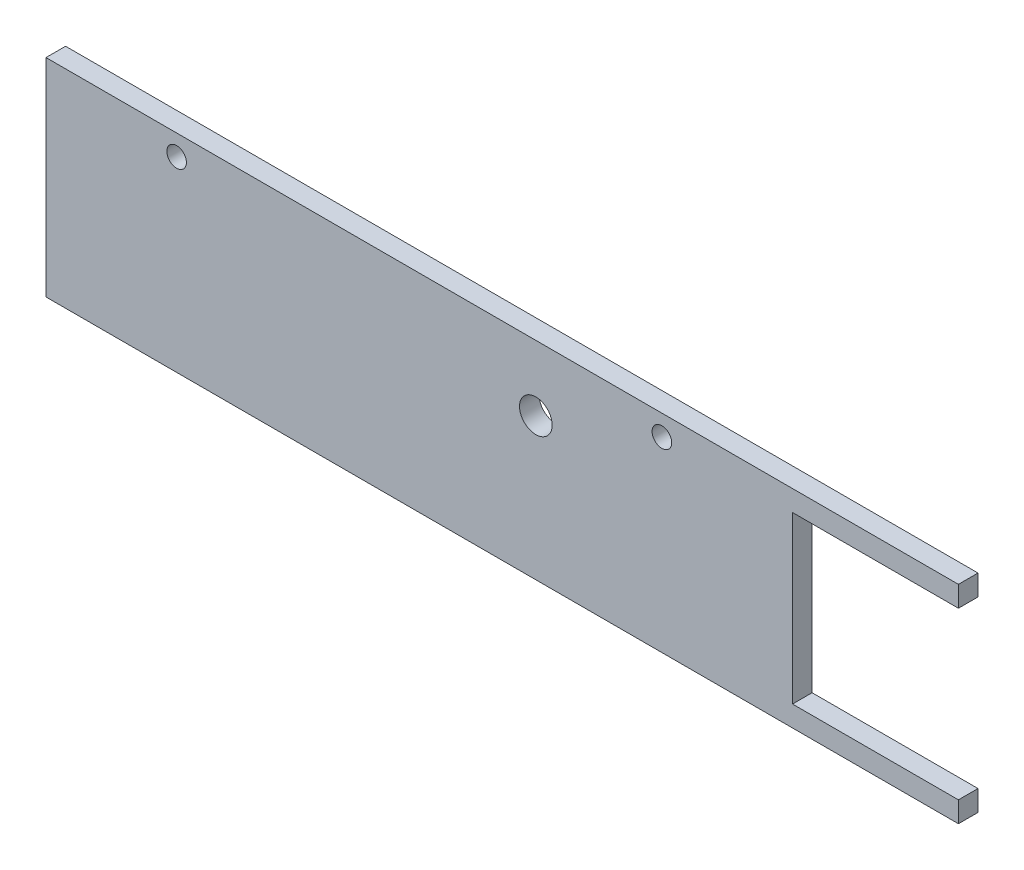
SolidWorks part; units mm, degrees
material "PET"
ref_plane "Front Plane" through (0, 0, 0) normal (0, 0, 1) x (1, 0, 0)
ref_plane "Top Plane" through (0, 0, 0) normal (0, 1, 0) x (1, 0, 0)
ref_plane "Right Plane" through (0, 0, 0) normal (1, 0, 0) x (0, 0, -1)
sketch "Sketch2" plane through (0, 0, 0) normal (0, 0, 1) x (1, 0, 0)
  line L1 (0, 0) -> (-139.7, 0)
  line L2 (0, 0) -> (0, -31.75)
  line L3 (0, -31.75) -> (-139.7, -31.75)
  line L4 (-139.7, 0) -> (-139.7, -31.75)
  dimension "D1" = 31.75
  dimension "D2" = 139.7
extrude "Boss-Extrude1" add sketch "Sketch2" along normal blind 3
sketch "Sketch3" plane through (0, 0, 3) normal (0, 0, 1) x (1, 0, 0)
  line L0 (0, -31.75) -> (0, 0) construction
  line L2 (0, -3.175) -> (-25.4, -3.175)
  line L3 (0, -3.175) -> (0, -28.575)
  line L4 (0, -28.575) -> (-25.4, -28.575)
  line L5 (-25.4, -3.175) -> (-25.4, -28.575)
  point P0 (0, -3.175)
  point P1 (0, -28.575)
  dimension "D1" = 3.175
  dimension "D2" = 25.4
  dimension "D3" = 25.4
extrude "Cut-Extrude1" cut sketch "Sketch3" against normal through all
sketch "Sketch8" plane through (0, 0, 3) normal (0, 0, 1) x (1, 0, 0)
  line L0 (-25.4, -3.175) -> (-25.4, -28.575) construction
  line L1 (-139.7, 0) -> (-119.7, 0) construction
  line L2 (-139.7, 0) -> (-139.7, -3.175) construction
  line L3 (-139.7, -3.175) -> (-119.7, -3.175) construction
  line L4 (-119.7, 0) -> (-119.7, -3.175) construction
  line L17 (-25.4, -13.7971) -> (-25.4, 0) construction
  line L18 (0, 0) -> (-139.7, 0) construction
  line L19 (-139.7, 0) -> (-139.7, -31.75) construction
  line L20 (-25.4, 0) -> (-45.4, 0) construction
  line L21 (-25.4, 0) -> (-25.4, -3.175) construction
  line L22 (-25.4, -3.175) -> (-45.4, -3.175) construction
  line L23 (-45.4, 0) -> (-45.4, -3.175) construction
  line L24 (-25.4, 0) -> (-64.7, 0) construction
  line L25 (-25.4, 0) -> (-25.4, -24.6382) construction
  line L27 (-64.7, 0) -> (-64.7, -10) construction
  circle A0 centre (-64.7, -10) radius 2.5
  dimension "D3" = 5
  dimension "D1" = 3.175
  dimension "D2" = 10
  dimension "D4" = 75
  dimension "D5" = 20
  dimension "D6" = 20
  dimension "D7" = 20
sketch "Sketch9" plane through (0, 0, 3) normal (0, 0, 1) x (1, 0, 0)
  circle A0 centre (-119.7, -3.175) radius 1.5
  circle A1 centre (-45.4, -3.175) radius 1.5
  dimension "D1" = 3
  dimension "D2" = 3
extrude "Cut-Extrude4" cut sketch "Sketch9" against normal blind 6.35 and the other way through all
extrude "Cut-Extrude5" cut sketch "Sketch8" against normal through all both contours A0
hole_wizard "Ø3.0mm Dowel Hole2" positions "Sketch12" profile "Sketch13" hole size "Ø3.0" standard "ANSI Metric"
sketch "Sketch12" plane through (-146.05, -31.75, 0) normal (0, 0, 1) x (1, 0, 0)
  point P0 (26.35, 28.575)
  point P3 (100.65, 28.575)
sketch "Sketch13" plane through (-119.7, -3.175, 0) normal (1, 0, 0) x (0, -1, 0)
  line L0 (0, 0) -> (0, 7.2513)
  line L1 (0, 7.2513) -> (1.5, 6.35)
  line L2 (1.5, 6.35) -> (1.5, 0)
  line L3 (1.5, 0) -> (0, 0)
  line L4 (0, 7.2513) -> (-1.5, 6.35) construction
  line L5 (0, -6.35) -> (0, 107.95) construction
  dimension "Hole Dia." = 3
  dimension "Hole Depth" = 6.35
  dimension "Drill Angle" = 118
equation "\"width\" = 6in 'side to side 6"
equation "\"height\"= 1.25in'top to bottom from 1.25"
equation "\"length\"=6.25in 'back to front 6.25"
equation "\"side_width\"= 1in"
equation "\"wheel_di\"=1.875in'2.375"
equation "\"wepon_di\" = 1.25in ' milled rectangle must compensate for bolts ~ - .5 1.5"
equation "\"wepon_axle\" = 0.1in ' placement from front .5"
equation "\"frame_bolts\" = 0.125"
equation "\"wheel_base\"= 2.5in"
equation "\"D2@Sketch2\"=\"width\"-.5in"
equation "\"D1@Sketch2\"=\"height\""
